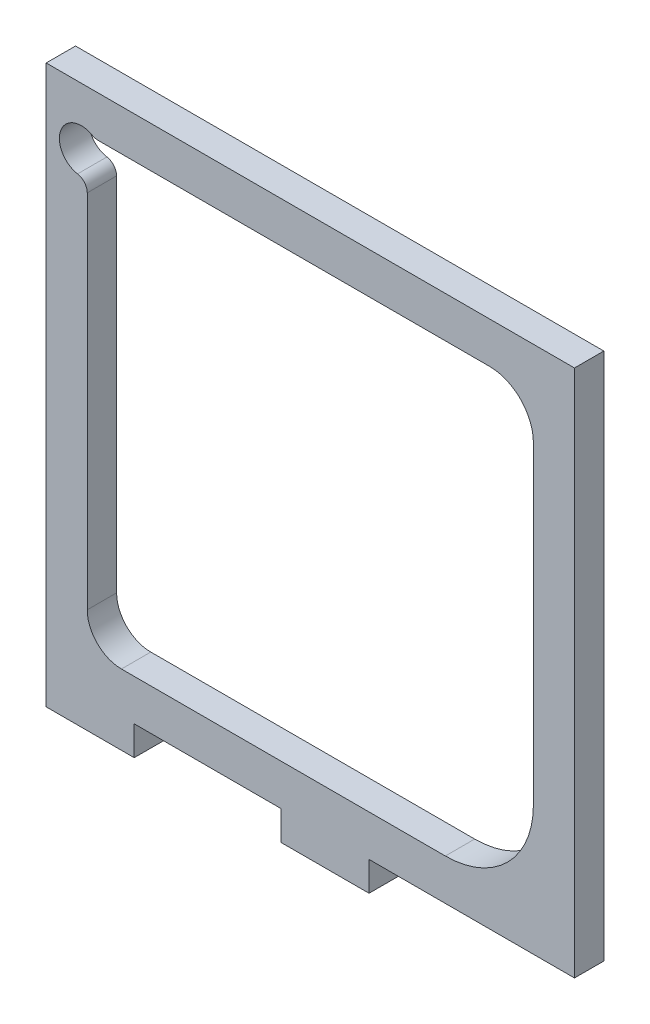
SolidWorks part; units mm, degrees
ref_plane "Front Plane" through (0, 0, 0) normal (0, 0, 1) x (1, 0, 0)
ref_plane "Top Plane" through (0, 0, 0) normal (0, 1, 0) x (1, 0, 0)
ref_plane "Right Plane" through (0, 0, 0) normal (1, 0, 0) x (0, 0, -1)
sketch "Sketch1" plane through (0, 0, 0) normal (0, 0, 1) x (1, 0, 0)
  line L0 (-57.15, -57.15) -> (57.15, -57.15)
  line L1 (-57.15, -57.15) -> (-57.15, 57.15)
  line L2 (-57.15, 57.15) -> (57.15, 57.15)
  line L3 (57.15, -57.15) -> (57.15, 57.15)
  line L5 (-57.15, 0) -> (57.15, 0) construction
  line L7 (0, 57.15) -> (0, -57.15) construction
  line L8 (-40.8649, -48.26) -> (17.088, -48.26)
  line L9 (-48.26, -40.8649) -> (-48.26, 4.6862)
  line L10 (48.26, -17.5136) -> (48.26, 38.735)
  line L11 (-48.26, -48.26) -> (59.1365, 59.1365) construction
  line L13 (12.3175, 48.26) -> (38.735, 48.26)
  line L14 (48.26, -17.5136) -> (48.26, -48.26) construction
  line L15 (17.088, -48.26) -> (48.26, -48.26) construction
  line L16 (-48.26, 4.6862) -> (-48.26, 37.2588)
  line L17 (-45.9239, 48.26) -> (12.3175, 48.26)
  line L19 (17.088, -48.26) -> (29.21, -48.26)
  line L20 (48.26, -17.5136) -> (48.26, -29.21)
  arc A9 (-40.8649, -48.26) -> (-48.26, -40.8649) centre (-40.8649, -40.8649) cw
  arc A12 (38.735, 48.26) -> (48.26, 38.735) centre (38.735, 38.735) cw
  arc A16 (29.21, -48.26) -> (48.26, -29.21) centre (29.21, -29.21) ccw
  arc A18 (-47.1782, 48.5913) -> (-50.3583, 39.7601) centre (-49.53, 44.45) ccw
  arc A19 (-45.9239, 48.26) -> (-47.1782, 48.5913) centre (-45.9239, 50.8) cw
  arc A20 (-48.26, 37.2588) -> (-50.3583, 39.7601) centre (-50.8, 37.2588) ccw
  point P0 (0, 0)
  point P1 (0, 0)
  point P16 (0, 0)
  dimension "D4" = 9.525
  dimension "D9" = 8.89
  dimension "D11" = 8.89
  dimension "D12" = 8.89
  dimension "D5" = 2.54
  dimension "D8" = 19.05
  dimension "D10" = 9.525
  dimension "D2" = 7.62
  dimension "D3" = 12.7
  dimension "D6" = 8.89
  dimension "D7" = 114.3
extrude "Boss-Extrude1" add sketch "Sketch1" along normal mid plane 6.35
sketch "Sketch2" plane through (0, -57.15, 0) normal (0, -1, 0) x (1, 0, 0)
  line L0 (-57.15, -3.175) -> (57.15, -3.175) construction
  line L1 (12.7, 3.175) -> (-6.35, 3.175)
  line L2 (12.7, 3.175) -> (12.7, -3.175)
  line L3 (12.7, -3.175) -> (-6.35, -3.175)
  line L4 (-6.35, 3.175) -> (-6.35, -3.175)
  line L5 (-57.15, 3.175) -> (57.15, 3.175) construction
  line L6 (-38.1, 3.175) -> (-57.15, 3.175)
  line L7 (-38.1, 3.175) -> (-38.1, -3.175)
  line L8 (-38.1, -3.175) -> (-57.15, -3.175)
  line L9 (-57.15, 3.175) -> (-57.15, -3.175)
  line L10 (-57.15, 3.175) -> (-57.15, -3.175) construction
  dimension "D1" = 19.05
  dimension "D2" = 31.75
extrude "Boss-Extrude2" add sketch "Sketch2" along normal blind 6.35
sketch "Sketch3" plane through (0, 0, -3.175) normal (0, 0, -1) x (-1, 0, 0)
  line L0 (57.15, 57.15) -> (57.15, -63.5) construction
  line L1 (57.15, 44.45) -> (63.5, 44.45)
  line L2 (57.15, 44.45) -> (57.15, 19.05)
  line L3 (57.15, 19.05) -> (63.5, 19.05)
  line L4 (63.5, 44.45) -> (63.5, 19.05)
  line L5 (-57.15, 57.15) -> (57.15, 57.15) construction
  point P6 (60.325, 44.45)
  dimension "D1" = 25.4
  dimension "D2" = 6.35
  dimension "D3" = 12.7
extrude "Boss-Extrude3" [suppressed] add sketch "Sketch3" against normal blind 6.35
